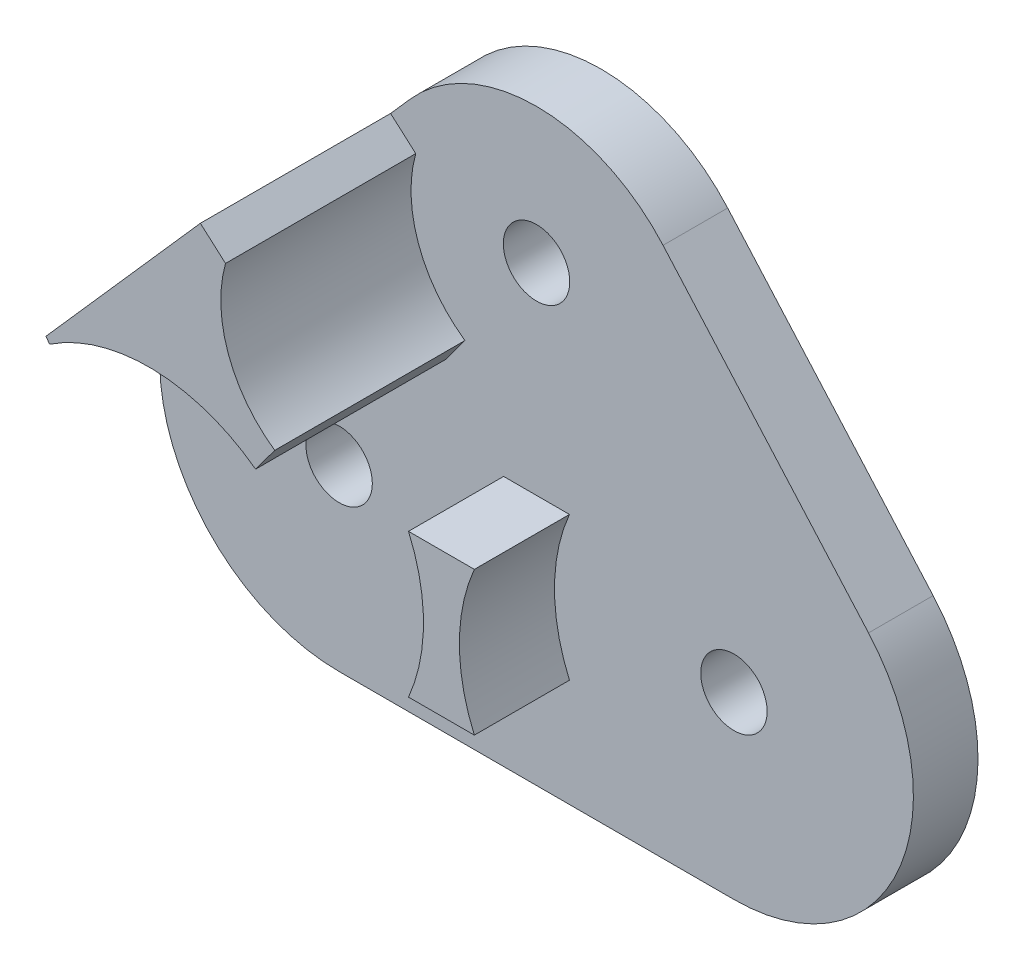
SolidWorks part; units mm, degrees
note: The reader was unsure of these and kept them because the rebuilt part matched: shared geometry of "草图3<3>".
ref_plane "前视基准面" through (0, 0, 0) normal (0, 0, 1) x (1, 0, 0)
ref_plane "上视基准面" through (0, 0, 0) normal (0, 1, 0) x (1, 0, 0)
ref_plane "右视基准面" through (0, 0, 0) normal (1, 0, 0) x (0, 0, -1)
sketch "草图1" plane through (0, 0, 0) normal (0, 0, 1) x (1, 0, 0)
  line L0 (-8.55, 3.25) -> (2.45, 3.25) construction
  line L1 (-8.55, 8.25) -> (2.45, 8.25)
  line L2 (-8.55, -1.75) -> (2.45, -1.75)
  arc A0 (-8.55, 8.25) -> (-8.55, -1.75) centre (-8.55, 3.25) ccw
  arc A1 (2.45, -1.75) -> (2.45, 8.25) centre (2.45, 3.25) ccw
  circle A2 centre (-8.55, 3.25) radius 0.925
  circle A3 centre (2.45, 3.25) radius 0.925
  point P2 (-3.05, 3.25)
  dimension "D1" = 5
  dimension "D2" = 11
extrude "凸台-拉伸1" add sketch "草图1" along normal blind 1.8
sketch "草图2" plane through (0, 0, 1.8) normal (0, 0, 1) x (1, 0, 0)
  line L0 (-12.2996, 6.5576) -> (-6.5749, 13.0474)
  line L1 (-3.05, -1.75) -> (-3.05, 18.9539) construction
  line L2 (-8.55, -1.75) -> (2.45, -1.75) construction
  line L3 (6.1996, 6.5576) -> (0.4749, 13.0474)
  line L4 (2.45, 8.25) -> (-8.55, 8.25) construction
  line L5 (2.45, 8.25) -> (-8.55, 8.25)
  arc A1 (0.4749, 13.0474) -> (-6.5749, 13.0474) centre (-3.05, 9.9381) ccw
  arc A2 (-8.55, 8.25) -> (-8.55, -1.75) centre (-8.55, 3.25) ccw construction
  arc A3 (2.45, -1.75) -> (2.45, 8.25) centre (2.45, 3.25) ccw construction
  arc A4 (-8.55, 8.25) -> (-8.55, -1.75) centre (-8.55, 3.25) ccw construction
  arc A5 (6.1996, 6.5576) -> (2.45, 8.25) centre (2.45, 3.25) ccw
  arc A6 (-8.55, 8.25) -> (-12.2996, 6.5576) centre (-8.55, 3.25) ccw
  circle A7 centre (-3.05, 10.8631) radius 0.925
extrude "凸台-拉伸2" add sketch "草图2" against normal blind 1.8
sketch "草图3" plane through (0, 0, 1.8) normal (0, 0, 1) x (1, 0, 0)
  line L0 (-11.4169, 7.5583) -> (-11.32, 7.4126)
  line L1 (-6.5749, 13.0474) -> (-12.2996, 6.5576) construction
  line L2 (-11.4169, 7.5583) -> (-7.1162, 12.4338)
  line L3 (-7.1162, 12.4338) -> (-6.4151, 11.8153)
  line L4 (-5.0444, 7.9902) -> (-5.577, 7.2701)
  line L5 (-3.9674, 5.25) -> (-2.1326, 5.25)
  line L6 (-3.9674, 1.25) -> (-2.1326, 1.25)
  arc A0 (-6.4151, 11.8153) -> (-5.0444, 7.9902) centre (-3.05, 10.8631) ccw
  arc A2 (-5.577, 7.2701) -> (-11.32, 7.4126) centre (-8.55, 3.25) ccw
  arc A4 (-3.9674, 1.25) -> (-3.9674, 5.25) centre (-8.55, 3.25) ccw
  arc A5 (-2.1326, 5.25) -> (-2.1326, 1.25) centre (2.45, 3.25) ccw
  dimension "D2" = 2
extrude "凸台-拉伸3" add sketch "草图3" along normal blind 5.3
extrude "凸台-拉伸4" add sketch "草图3<3>" along normal blind 2.65 contours A5 L5 A4 L6
sketch "草图3<3>" plane through (0, 0, 1.8) normal (0, 0, 1) x (1, 0, 0) same geometry as "草图3"
